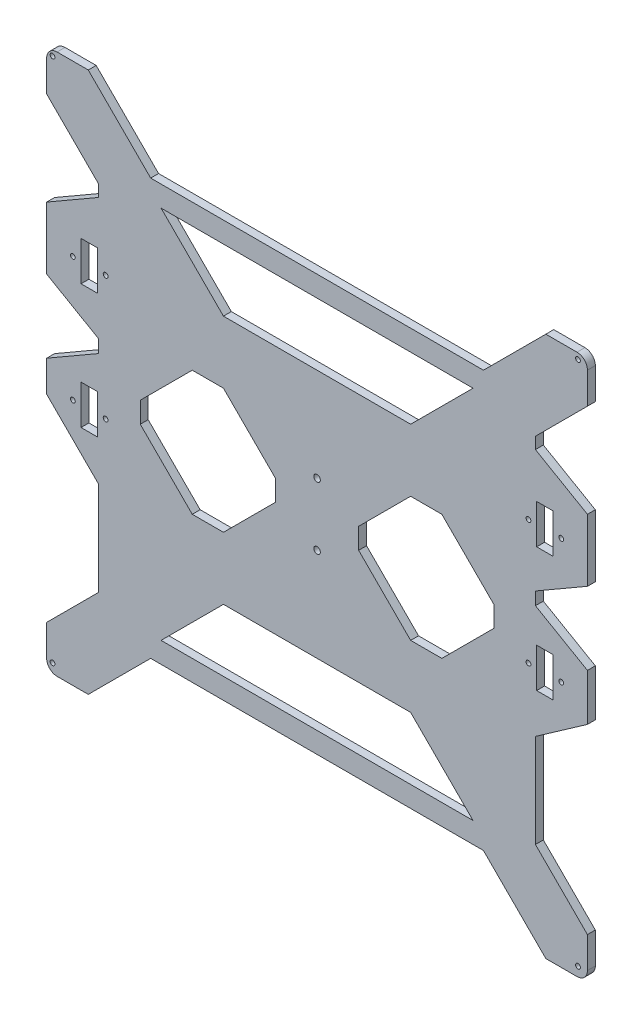
SolidWorks part; units mm, degrees
material "5052-H32"
ref_plane "Front Plane" through (0, 0, 0) normal (0, 0, 1) x (1, 0, 0)
ref_plane "Top Plane" through (0, 0, 0) normal (0, 1, 0) x (1, 0, 0)
ref_plane "Right Plane" through (0, 0, 0) normal (1, 0, 0) x (0, 0, -1)
sketch "Model" plane through (0, 0, 0) normal (0, 0, 1) x (1, 0, 0)
  line L0 (38.5361, 132.6139) -> (38.5361, 132.4727)
  line L1 (38.5361, -178.6774) -> (38.5361, -178.7219)
  line L2 (-253.5639, -197.5861) -> (-253.5639, -197.7273)
  line L3 (-290.6813, -31.2683) -> (-258.9313, -12.9374)
  line L4 (-258.9313, -82.0683) -> (-258.9313, -139.2183)
  line L5 (38.5361, 132.6139) -> (38.5361, 132.4727)
  line L6 (38.5361, -178.6774) -> (38.5361, -178.7219)
  line L7 (7.7687, -139.2183) -> (7.7687, -82.0683)
  line L8 (39.5187, -59.8367) -> (39.5187, -31.2683)
  line L9 (-23.9813, 95.7317) -> (-227.1813, 95.7317)
  line L10 (-290.6813, 108.4317) -> (-258.9313, 76.6817)
  line L11 (-30.3313, -145.5683) -> (-68.4313, -107.4683)
  line L12 (-23.9813, -158.2683) -> (14.1187, -196.3683)
  line L13 (39.5187, 108.4317) -> (39.5187, 127.4817)
  line L14 (-227.1813, 95.7317) -> (-265.2813, 133.8317)
  line L15 (-220.8313, 83.0317) -> (-182.7313, 44.9317)
  line L16 (-274.6813, -45.4288) -> (-254.6813, -45.4288) construction
  line L17 (39.5187, -170.9683) -> (7.7687, -139.2183)
  line L18 (-265.2813, -196.3683) -> (-227.1813, -158.2683)
  line L19 (-182.7313, -107.4683) -> (-68.4313, -107.4683)
  line L20 (-264.6813, -45.4288) -> (-264.6813, -43.5832) construction
  line L21 (7.7687, 76.6817) -> (39.5187, 108.4317)
  line L22 (-23.9813, 95.7317) -> (14.1187, 133.8317)
  line L23 (-30.3313, 83.0317) -> (-68.4313, 44.9317)
  line L24 (39.5187, -31.2683) -> (7.7687, -12.9374)
  line L25 (-258.9313, -139.2183) -> (-290.6813, -170.9683)
  line L26 (-182.7313, 44.9317) -> (-68.4313, 44.9317)
  line L27 (-220.8313, -145.5683) -> (-182.7313, -107.4683)
  line L28 (-220.8313, -145.5683) -> (-30.3313, -145.5683)
  line L29 (-258.9313, -82.0683) -> (-290.6813, -50.3183)
  line L30 (-290.6813, -31.2683) -> (-290.6813, -50.3183)
  line L31 (-274.6813, -43.9683) -> (-274.6813, -31.2683) construction
  line L32 (-258.9313, -12.9374) -> (-258.9313, -5.1492)
  line L33 (-201.7813, -69.3683) -> (-233.5313, -37.6183)
  line L34 (-182.7313, -69.3683) -> (-201.7813, -69.3683)
  line L35 (7.7687, -12.9374) -> (7.7687, -5.1492)
  line L36 (7.7687, -5.1492) -> (39.5187, 13.1817)
  line L37 (-150.9813, -37.6183) -> (-182.7313, -69.3683)
  line L38 (39.5187, -59.8367) -> (10.4646, -80.1806)
  line L39 (10.4646, -80.1806) -> (7.7687, -82.0683)
  line L40 (-100.1813, -37.6183) -> (-100.1813, -24.9183)
  line L41 (-150.9813, -37.6183) -> (-150.9813, -24.9183)
  line L42 (-150.9813, -24.9183) -> (-182.7313, 6.8317)
  line L43 (-182.7313, 6.8317) -> (-201.7813, 6.8317)
  line L44 (-201.7813, 6.8317) -> (-233.5313, -24.9183)
  line L45 (-233.5313, -24.9183) -> (-233.5313, -37.6183)
  line L46 (-17.6313, -24.9183) -> (-17.6313, -37.6183)
  line L47 (-49.3813, 6.8317) -> (-17.6313, -24.9183)
  line L48 (-220.8313, 83.0317) -> (-30.3313, 83.0317)
  line L49 (-68.4313, 6.8317) -> (-49.3813, 6.8317)
  line L50 (-100.1813, -24.9183) -> (-68.4313, 6.8317)
  line L51 (-100.1813, -37.6183) -> (-68.4313, -69.3683)
  line L52 (-68.4313, -69.3683) -> (-49.3813, -69.3683)
  line L53 (-49.3813, -69.3683) -> (-17.6313, -37.6183)
  line L54 (39.5187, 13.1817) -> (39.5187, 51.2817)
  line L55 (39.5187, 51.2817) -> (7.7687, 69.6126)
  line L56 (7.7687, 69.6126) -> (7.7687, 76.6817)
  line L57 (-258.9313, -5.1492) -> (-290.6813, 13.1817)
  line L58 (-265.2813, -196.3683) -> (-284.3313, -196.3683)
  line L59 (-290.6813, -190.0183) -> (-290.6813, -170.9683)
  line L60 (-290.6813, 108.4317) -> (-290.6813, 127.4817)
  line L61 (-284.3313, 133.8317) -> (-265.2813, 133.8317)
  line L62 (14.1187, 133.8317) -> (33.1687, 133.8317)
  line L63 (-290.6813, 13.1817) -> (-290.6813, 51.2817)
  line L64 (39.5187, -170.9683) -> (39.5187, -190.0183)
  line L65 (33.1687, -196.3683) -> (14.1187, -196.3683)
  line L66 (-258.9313, 76.6817) -> (-258.9313, 69.6126)
  line L67 (-258.9313, 69.6126) -> (-290.6813, 51.2817)
  line L68 (-274.6813, 30.5682) -> (-254.6813, 30.5682) construction
  line L69 (-254.6813, 30.5682) -> (23.5187, 30.5682) construction
  line L70 (23.5187, 30.5682) -> (23.5187, -45.4288) construction
  line L71 (-227.1813, -158.2683) -> (-23.9813, -158.2683)
  line L72 (38.5361, -178.6774) -> (38.5361, -178.7219)
  line L73 (3.5187, 30.5682) -> (3.5187, -45.4288) construction
  line L74 (-227.1813, -158.2683) -> (-23.9813, -158.2683)
  line L75 (38.5361, -178.6774) -> (38.5361, -178.7219)
  line L76 (-274.6813, 30.5682) -> (-274.6813, -45.4288) construction
  line L77 (-125.5813, 95.7317) -> (-125.5813, -158.2683) construction
  line L78 (-290.6813, -31.2683) -> (39.5187, -31.2683) construction
  arc A0 (33.1687, -196.3683) -> (39.5187, -190.0183) centre (33.1687, -190.0183) ccw
  arc A1 (-290.6813, -190.0183) -> (-284.3313, -196.3683) centre (-284.3313, -190.0183) ccw
  arc A2 (-290.6813, 127.4817) -> (-284.3313, 133.8317) centre (-284.3313, 127.4817) cw
  arc A3 (33.1687, 133.8317) -> (39.5187, 127.4817) centre (33.1687, 127.4817) cw
  circle A4 centre (-287.1253, -190.6025) radius 1.4605
  circle A5 centre (33.7529, -190.6025) radius 1.4605
  circle A6 centre (33.7529, 130.2757) radius 1.4605
  circle A7 centre (-287.1253, 130.2757) radius 1.4605
  circle A8 centre (-274.6813, -45.4288) radius 1.4605
  circle A9 centre (-254.6813, -45.4288) radius 1.4605
  circle A10 centre (23.5187, -45.4288) radius 1.4605
  circle A11 centre (3.5187, -45.4288) radius 1.4605
  circle A12 centre (23.5187, 30.5682) radius 1.4605
  circle A13 centre (3.5187, 30.5682) radius 1.4605
  circle A14 centre (-254.6813, 30.5682) radius 1.4605
  circle A15 centre (-274.6813, 30.5682) radius 1.4605
  circle A16 centre (-125.5813, -12.2183) radius 2
  circle A17 centre (-125.5813, -50.3183) radius 2
  point P72 (-125.5813, -31.2683)
  point P114 (-125.5813, 83.0317)
  point P120 (-233.5313, -31.2683)
  point P129 (-150.9813, -31.2683)
  point P149 (-125.5813, 44.9317)
  point P156 (-17.6313, -31.2683)
  dimension "D28" = 6.35
  dimension "D29" = 6.35
  dimension "D30" = 6.35
  dimension "D31" = 6.35
  dimension "D35" = 2.921
  dimension "D36" = 2.921
  dimension "D37" = 2.921
  dimension "D38" = 2.921
  dimension "D53" = 2.921
  dimension "D54" = 2.921
  dimension "D56" = 4
  dimension "D57" = 4
  dimension "D1" = 330.2
  dimension "D2" = 330.2
  dimension "D3" = 135
  dimension "D4" = 135
  dimension "D5" = 38.1
  dimension "D6" = 135
  dimension "D7" = 120
  dimension "D8" = 19.05
  dimension "D9" = 135
  dimension "D10" = 19.05
  dimension "D11" = 31.75
  dimension "D12" = 190.5
  dimension "D13" = 114.3
  dimension "D14" = 38.1
  dimension "D15" = 114.3
  dimension "D16" = 135
  dimension "D17" = 6.35
  dimension "D18" = 38.1
  dimension "D19" = 135
  dimension "D20" = 135
  dimension "D21" = 6.35
  dimension "D22" = 19.05
  dimension "D23" = 25.4
  dimension "D24" = 50.8
  dimension "D25" = 120
  dimension "D26" = 135
  dimension "D27" = 127
  dimension "D32" = 19.05
  dimension "D33" = 19.05
  dimension "D34" = 19.05
  dimension "D39" = 120
  dimension "D40" = 19.05
  dimension "D41" = 120
  dimension "D42" = 120
  dimension "D43" = 50.8
  dimension "D44" = 19.05
  dimension "D45" = 31.75
  dimension "D46" = 125
  dimension "D47" = 320.8782
  dimension "D48" = 320.8782
  dimension "D49" = 3.556
  dimension "D50" = 3.556
  dimension "D51" = 20
  dimension "D52" = 26
  dimension "D55" = 12.7
  dimension "D58" = 38.1
  dimension "D59" = 19.05
  dimension "D60" = 82.55
  dimension "D61" = 38.1
  dimension "D63" = 120
  dimension "D64" = 38.1
  dimension "D65" = 82.55
  dimension "D67" = 75.997
extrude "Boss-Extrude1" add sketch "Model" along normal mid plane 4.826 contours A3 L62 L22 L9 L14 L61 A2 L60 L10 L30 L29 L4 L25 L59 A1 L58 L18 L71 L12 L65 A0 L64 L17 L7 L39 L38 L8 L21 L13 A17 A16 A14 A13 A12 A10 A9 region at (-125.199, -28.2686, 0)
sketch "Sketch1" plane through (0, 0, 2.413) normal (0, 0, 1) x (1, 0, 0)
  line L0 (23.5187, 30.5682) -> (23.5187, 17.7506) construction
  line L1 (-269.6813, -33.4288) -> (-259.6813, -33.4288)
  line L2 (-269.6813, -33.4288) -> (-269.6813, -57.4288)
  line L3 (-269.6813, -57.4288) -> (-259.6813, -57.4288)
  line L4 (-259.6813, -33.4288) -> (-259.6813, -57.4288)
  line L5 (-269.6813, 42.5712) -> (-259.6813, 42.5712)
  line L6 (-269.6813, 42.5712) -> (-269.6813, 18.5712)
  line L7 (-269.6813, 18.5712) -> (-259.6813, 18.5712)
  line L8 (-259.6813, 42.5712) -> (-259.6813, 18.5712)
  line L9 (8.5187, 42.5712) -> (18.5187, 42.5712)
  line L10 (8.5187, 42.5712) -> (8.5187, 18.5712)
  line L11 (8.5187, 18.5712) -> (18.5187, 18.5712)
  line L12 (18.5187, 42.5712) -> (18.5187, 18.5712)
  line L13 (8.5187, -33.4288) -> (18.5187, -33.4288)
  line L14 (8.5187, -33.4288) -> (8.5187, -57.4288)
  line L15 (8.5187, -57.4288) -> (18.5187, -57.4288)
  line L16 (18.5187, -33.4288) -> (18.5187, -57.4288)
  circle A1 centre (-274.6813, -45.4288) radius 1.4605 construction
  circle A5 centre (-274.6813, 30.5682) radius 1.4605 construction
  circle A8 centre (23.5187, 30.5682) radius 1.4605 construction
  circle A9 centre (23.5187, -45.4288) radius 1.4605 construction
  point P20 (13.5187, 42.5712)
  dimension "D3" = 12
  dimension "D4" = 5
  dimension "D5" = 10
  dimension "D8" = 100
  dimension "D11" = 100
  dimension "D15" = 12
  dimension "D1" = 10
  dimension "D2" = 24
  dimension "D6" = 24
  dimension "D7" = 5
  dimension "D9" = 24
  dimension "D10" = 5
  dimension "D12" = 10
  dimension "D13" = 10
  dimension "D14" = 24
  dimension "D16" = 5
extrude "Cut-Extrude1" cut sketch "Sketch1" against normal blind 10
